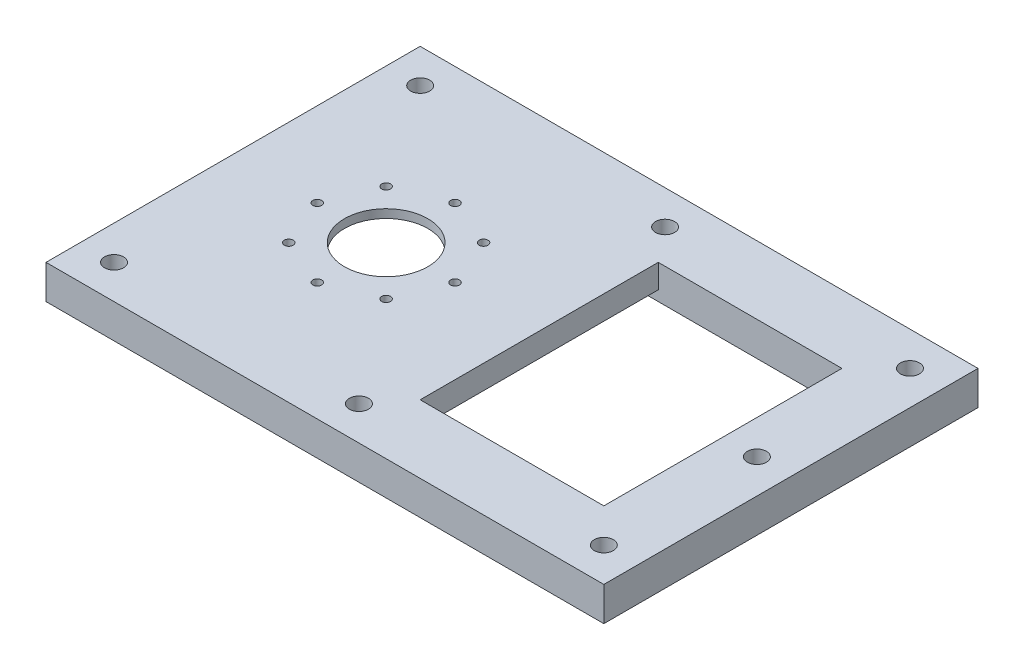
SolidWorks part; units mm, degrees
ref_plane "Front Plane" through (0, 0, 0) normal (0, 0, 1) x (1, 0, 0)
ref_plane "Top Plane" through (0, 0, 0) normal (0, 1, 0) x (1, 0, 0)
ref_plane "Right Plane" through (0, 0, 0) normal (1, 0, 0) x (0, 0, -1)
sketch "Sketch1" plane through (0, 0, 0) normal (0, 1, 0) x (1, 0, 0)
  circle A0 centre (0, 0) radius 12.25
  circle A1 centre (0, 0) radius 35
  dimension "D1" = 70
extrude "Boss-Extrude1" add sketch "Sketch1" along normal blind 2.5 contours A0 | A1
sketch "Sketch3" plane through (0, 0, 0) normal (0, -1, 0) x (1, 0, 0)
  circle A0 centre (0, 0) radius 18.6
  circle A3 centre (0, 0) radius 35 construction
  circle A4 centre (0, 0) radius 35
  dimension "D1" = 37.2
extrude "Boss-Extrude2" add sketch "Sketch3" along normal blind 2 contours A0 | A4
sketch "Sketch4" plane through (0, -2, 0) normal (0, -1, 0) x (1, 0, 0)
  circle A0 centre (0, 0) radius 22.3
  circle A2 centre (0, 0) radius 35 construction
  circle A3 centre (0, 0) radius 35
extrude "Boss-Extrude3" add sketch "Sketch4" along normal blind 2
sketch "Sketch6" plane through (0, 2.5, 0) normal (0, 1, 0) x (1, 0, 0)
  circle A0 centre (0, 0) radius 20.25 construction
  circle A1 centre (0, 20.25) radius 1.3
  circle A2 centre (14.3189, 14.3189) radius 1.3
  circle A3 centre (20.25, 0) radius 1.3
  circle A4 centre (14.3189, -14.3189) radius 1.3
  circle A5 centre (0, -20.25) radius 1.3
  circle A6 centre (-14.3189, -14.3189) radius 1.3
  circle A7 centre (-20.25, 0) radius 1.3
  circle A8 centre (-14.3189, 14.3189) radius 1.3
  point P22 (0, 0)
  dimension "D1" = 40.5
  dimension "D2" = 2.6
  dimension "D3" = 8
extrude "Cut-Extrude1" cut sketch "Sketch6" against normal up to next contours A8 | A7 | A6 | A5 | A4 | A3 | A2 | A1
sketch "Sketch7" plane through (0, 2.5, 0) normal (0, 1, 0) x (1, 0, 0)
  line L0 (45, -35) -> (99, -35)
  line L1 (-45, 55) -> (99, 55)
  line L2 (-45, 55) -> (-45, 35)
  line L3 (-45, 35) -> (99, 35) construction
  line L4 (99, 55) -> (99, 35) construction
  line L5 (99, 55) -> (119, 55)
  line L6 (99, 55) -> (99, -55) construction
  line L7 (99, -55) -> (119, -55)
  line L8 (119, 55) -> (119, -55)
  line L9 (-45, 35) -> (-35, 35) construction
  line L10 (-45, 35) -> (-45, -55)
  line L11 (-45, -55) -> (-35, -55)
  line L12 (-35, 35) -> (-35, -55) construction
  line L13 (-35, -55) -> (99, -55)
  line L14 (-35, -55) -> (-35, -35)
  line L15 (-35, -35) -> (99, -35) construction
  line L16 (99, -55) -> (99, -35) construction
  line L17 (35, 35) -> (45, 35) construction
  line L18 (35, 35) -> (35, -35) construction
  line L19 (35, -35) -> (45, -35) construction
  line L20 (45, 35) -> (45, -35)
  line L21 (99, -35) -> (99, 35)
  line L22 (99, 35) -> (45, 35)
  circle A0 centre (0, 0) radius 35
  circle A2 centre (0, 0) radius 35 construction
  circle M25 centre (0, 0) radius 35
  dimension "D2" = 10
  dimension "D1" = 20
  dimension "D3" = 64
  dimension "D4" = 20
  dimension "D5" = 20
  dimension "D6" = 10
extrude "Boss-Extrude6" add sketch "Sketch7" against normal blind 10 contours L11 L13 L7 L8 L5 L1 L2 L10 L22 L21 L0 L20 M25 region at (37.9694, 2.5, 0)
sketch "Sketch8" plane through (0, -7.5, 0) normal (0, -1, 0) x (1, 0, 0)
  line L1 (45, 35) -> (38, 35)
  line L2 (45, 35) -> (45, -35)
  line L3 (45, -35) -> (38, -35)
  line L4 (38, 35) -> (38, -35)
  line L5 (99, 35) -> (106, 35)
  line L6 (99, 35) -> (99, -35)
  line L7 (99, -35) -> (106, -35)
  line L8 (106, 35) -> (106, -35)
  point P12 (0, 0)
  line M12 (99, 35) -> (99, -35)
  dimension "D1" = 7
extrude "Cut-Extrude3" cut sketch "Sketch8" against normal blind 3 contours L8 L5 L7 M12 | L1 L4 L3 L2 region at (102.5, -7.5, 0)
sketch "Sketch10" plane through (0, 2.5, 0) normal (0, 1, 0) x (1, 0, 0)
  line L2 (-45, 45) -> (119, 45)
  line L3 (-45, 45) -> (119, 45) construction
  line L5 (-35, 55) -> (-35, -55)
  line L6 (-35, 55) -> (-35, -55) construction
  line L8 (-45, -45) -> (119, -45)
  line L9 (-45, -45) -> (119, -45) construction
  line L11 (109, 55) -> (109, -55)
  line L12 (109, 55) -> (109, -55) construction
  circle A0 centre (37, 45) radius 2.8
  circle A1 centre (-35, 45) radius 2.8
  circle A2 centre (-35, -45) radius 2.8
  circle A3 centre (37, -45) radius 2.8
  circle A4 centre (109, 45) radius 2.8
  circle A5 centre (109, -45) radius 2.8
  circle A6 centre (109, 0) radius 2.8
  point P22 (0, 0)
  dimension "D5" = 5.6
  dimension "D6" = 5.6
  dimension "D7" = 5.6
  dimension "D8" = 5.6
  dimension "D9" = 5.6
  dimension "D10" = 5.6
  dimension "D1" = 10
  dimension "D2" = 10
  dimension "D3" = 10
  dimension "D4" = 10
extrude "Cut-Extrude4" cut sketch "Sketch10" against normal up to next
